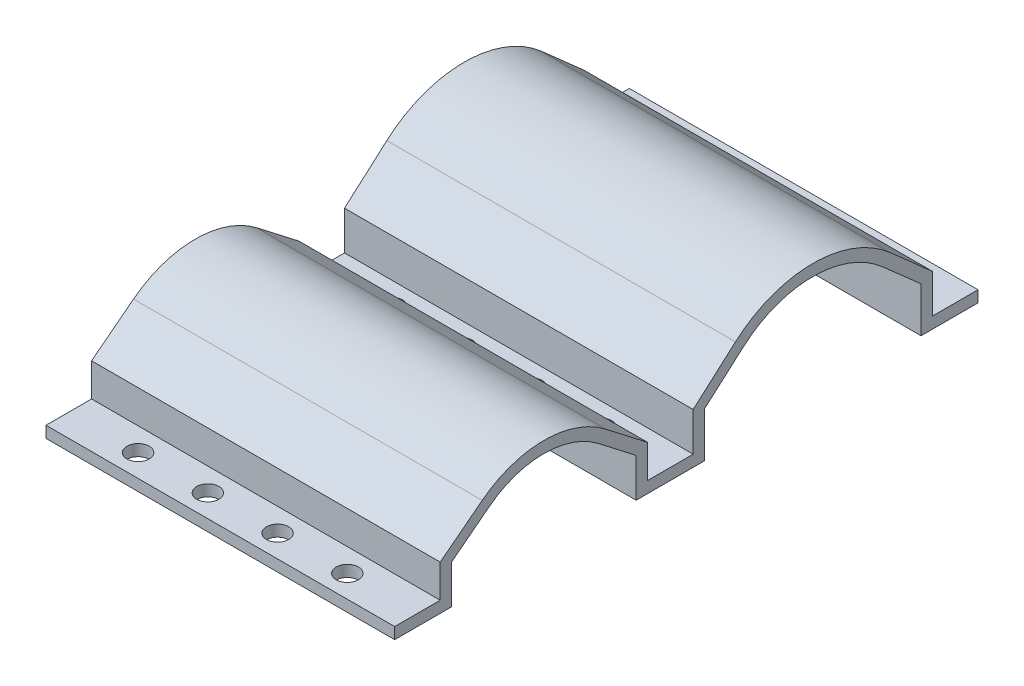
SolidWorks part; units mm, degrees
ref_plane "Front Plane" through (0, 0, 0) normal (0, 0, 1) x (1, 0, 0)
ref_plane "Top Plane" through (0, 0, 0) normal (0, 1, 0) x (1, 0, 0)
ref_plane "Right Plane" through (0, 0, 0) normal (1, 0, 0) x (0, 0, -1)
sketch "Sketch2" plane through (0, 0, 0) normal (1, 0, 0) x (0, 0, -1)
  line L0 (0, 0) -> (-10, 0)
  line L4 (-48, 0) -> (-60, 0)
  line L10 (-60, 6.8176) -> (-66.594, 11.9183)
  line L14 (-48, 7.8984) -> (-48, 0)
  line L16 (-10, 7.8984) -> (-10, 0)
  line L22 (-60, 6.8176) -> (-60, 0)
  line L27 (-41.2502, 13.863) -> (-48, 7.8984)
  line L31 (-85.806, 11.9183) -> (-92.4, 6.8176)
  line L32 (-92.4, 6.8176) -> (-92.4, 0)
  line L34 (-16.7498, 13.863) -> (-10, 7.8984)
  line L35 (-48, 0) -> (-10, 0) construction
  line L39 (-92.4, 0) -> (-60, 0) construction
  line L40 (-92.4, 0) -> (-102.4, 0)
  line L41 (0, 2) -> (-8, 2)
  line L42 (-50, 2) -> (-58, 2)
  line L43 (-58, 7.7991) -> (-58, 2)
  line L44 (-58, 7.7991) -> (-65.3703, 13.5003)
  line L45 (-87.0297, 13.5003) -> (-94.4, 7.7991)
  line L46 (-94.4, 7.7991) -> (-94.4, 2)
  line L47 (-8, 8.8001) -> (-8, 2)
  line L48 (-15.4254, 15.3617) -> (-8, 8.8001)
  line L49 (-42.5746, 15.3617) -> (-50, 8.8001)
  line L50 (-50, 8.8001) -> (-50, 2)
  line L51 (-94.4, 2) -> (-102.4, 2)
  line L52 (-102.4, 2) -> (-102.4, 0)
  line L53 (0, 2) -> (0, 0)
  line L54 (-8, 8.8001) -> (-8, 0) construction
  line L55 (0, 2) -> (-10, 2) construction
  line L56 (-48, 2) -> (-60, 2) construction
  line L57 (-50, 8.8001) -> (-50, 0) construction
  line L58 (-58, 7.7991) -> (-58, 0) construction
  line L59 (-92.4, 2) -> (-102.4, 2) construction
  line L60 (-94.4, 7.7991) -> (-94.4, 0) construction
  arc A4 (-65.3703, 13.5003) -> (-87.0297, 13.5003) centre (-76.2, -0.5) ccw
  arc A5 (-15.4254, 15.3617) -> (-42.5746, 15.3617) centre (-29, 0) ccw
  arc A8 (-16.7498, 13.863) -> (-41.2502, 13.863) centre (-29, 0) ccw
  arc A12 (-66.594, 11.9183) -> (-85.806, 11.9183) centre (-76.2, -0.5) ccw
  point P8 (-29, 18.5)
  point P9 (-76.2, 15.2)
  point P13 (-94.4, 7.7991)
  point P16 (-50, 8.8001)
  point P18 (-29, 0)
  point P44 (-76.2, 0)
  dimension "D3" = 15.7
  dimension "D5" = 18.5
  dimension "D1" = 18.5
  dimension "D4" = 12
  dimension "D6" = 10
  dimension "D2" = 15.2
  dimension "D7" = 32.4
  dimension "D8" = 38
  dimension "D9" = 2
extrude "Boss-Extrude1" add sketch "Sketch2" along normal blind 61.2
sketch "Sketch3" plane through (0, 2, 0) normal (0, 1, 0) x (1, 0, 0)
  line L2 (61.2, 0) -> (0, 0) construction
  line L3 (0, 0) -> (0, -8.1755) construction
  line L4 (61.2, 0) -> (61.2, -8.1755) construction
  line L5 (0, 0) -> (0, -8.1755) construction
  line L7 (0, -60) -> (0, -48) construction
  line L8 (61.2, 0) -> (0, 0) construction
  line L9 (61.2, -50) -> (0, -50) construction
  line L10 (0, -60) -> (0, -48) construction
  line L12 (61.2, -102.4) -> (0, -102.4) construction
  circle A0 centre (12.24, -3.93) radius 1.95
  circle A1 centre (24.48, -3.93) radius 1.95
  circle A2 centre (36.72, -3.93) radius 1.95
  circle A3 centre (48.96, -3.93) radius 1.95
  circle A4 centre (12.24, -53.9923) radius 1.95
  circle A5 centre (24.48, -53.9923) radius 1.95
  circle A6 centre (36.72, -53.9923) radius 1.95
  circle A7 centre (48.96, -53.9923) radius 1.95
  circle A8 centre (12.24, -98.47) radius 1.95
  circle A9 centre (24.48, -98.47) radius 1.95
  circle A10 centre (36.72, -98.47) radius 1.95
  circle A11 centre (48.96, -98.47) radius 1.95
  dimension "D1" = 3.9
  dimension "D4" = 12.24
  dimension "D5" = 12.24
  dimension "D6" = 12.24
  dimension "D3" = 12.24
  dimension "D2" = 3.93
  dimension "D9" = 3.9923
  dimension "D8" = 3.93
extrude "Cut-Extrude1" cut sketch "Sketch3" against normal up to surface (2 mm away) up to face at (30.6, 0, 54)
equation "\"MotorDIA\"= 37' Motor Diameter"
equation "\"SyringeDIA\"= 31.4'60ml Syringe Diameter"
equation "\"MotorShaftDIA\"= 6'Motor Shaft Dia"
equation "\"MotorKeyway\"= 1'Motor Shaft Keyway Depth"
equation "\"MotorLength\"= 56.7'Motor Length Excluding Shaft"
equation "\"SyringeLength\"= 117.3'60ml Syringe Length Excluding Nozzle"
equation "\"3Dtol\"= .5'Sizing Tolerance for 3D printed parts"
equation "\"ChamberDIA\"= 100 - 4'Buoyancy Chamber inner Diameter"
equation "\"ChamberThk\"= 2mm'Buoyancy Chamber Wall Thickness"
equation "\"BearingOD\"= 10"
equation "\"BearingID\"= 4"
equation "\"Bearingwidth\"= 4"
equation "\"ShaftDIA\"= 4"
equation "\"D1@Boss-Extrude1\"=\"MotorLength\"+\"3Dtol\"+4"
equation "\"D4@Sketch3\"=\"D3@Sketch3\""
equation "\"D5@Sketch3\"=\"D3@Sketch3\""
equation "\"D6@Sketch3\"=\"D3@Sketch3\""
equation "\"D3@Sketch3\"=\"D7@Sketch3\"/5"
equation "\"D3@Sketch2\"=\"SyringeDIA\"/2"
equation "\"D5@Sketch2\"=\"MotorDIA\"/2"
equation "\"D1@Sketch2\"=\"MotorDIA\"/2"
equation "\"D2@Sketch2\"=\"SyringeDIA\" / 2 - \"3Dtol\""
equation "\"D7@Sketch2\"=\"SyringeDIA\"+\"3Dtol\"*2"
equation "\"D8@Sketch2\"=\"MotorDIA\"+\"3Dtol\"*2"
